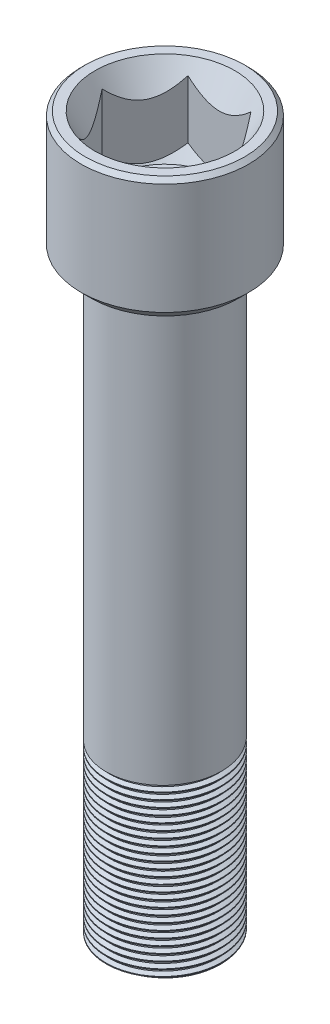
SolidWorks part; units mm, degrees
ref_plane "Front Plane" through (0, 0, 0) normal (0, 0, 1) x (1, 0, 0)
ref_plane "Top Plane" through (0, 0, 0) normal (0, 1, 0) x (1, 0, 0)
ref_plane "Right Plane" through (0, 0, 0) normal (1, 0, 0) x (0, 0, -1)
sketch "Sketch1" plane through (0, 0, 0) normal (0, 1, 0) x (1, 0, 0)
  circle A0 centre (0, 0) radius 4
  dimension "D1" = 8
extrude "Boss-Extrude1" add sketch "Sketch1" against normal blind 12
sketch "Sketch2" plane through (0, -12, 0) normal (0, -1, 0) x (1, 0, 0)
  circle A0 centre (0, 0) radius 2.75
  dimension "D1" = 5.5
extrude "Boss-Extrude2" add sketch "Sketch2" along normal blind 30
sketch "Sketch3" plane through (0, 0, 0) normal (0, 1, 0) x (1, 0, 0)
  line L1 (4.5, 0) -> (2.25, 3.8971)
  line L2 (2.25, 3.8971) -> (-2.25, 3.8971)
  line L3 (-2.25, 3.8971) -> (-4.5, 0)
  line L4 (-4.5, 0) -> (-2.25, -3.8971)
  line L5 (-2.25, -3.8971) -> (2.25, -3.8971)
  line L6 (2.25, -3.8971) -> (4.5, 0)
  circle A0 centre (0, 0) radius 3.8971 construction
  dimension "D1" = 4.5
extrude "Cut-Extrude1" cut sketch "Sketch3" against normal blind 6
chamfer "Chamfer2" distance 0.5 angle 45 1 edges at (0, -12, 4)
thread "Thread2" pitch 0.3175 method cut profile "Thread Profile6" start angle 0, offset 0, length 0, pitch 0.3175, diameter 5.5
ref_plane "Plane7" through (2.75, -42, 0) normal (0, 0, 1) x (1, 0, 0)
sketch "Thread Profile6" plane through (2.75, -42, 0) normal (0, 0, 1) x (1, 0, 0)
  line L0 (0, 0) -> (0, 0.3175) construction
  line L11 (0, 0) -> (0, 0.2778)
  line L12 (0, 0.2778) -> (-0.1719, 0.1786)
  line L13 (-0.1719, 0.1786) -> (-0.1719, 0.0992)
  line L15 (-0.1719, 0.0992) -> (0, 0)
  line L17 (-0.1719, 0.1389) -> (0, 0.1389) construction
  point P2 (0, 0)
  dimension "Pitch" = 0.3175
  dimension "Profile_Angle" = 60
  dimension "Profile_Land" = 0.0794
  dimension "Profile_Height" = 0.1719
sketch "Sketch59" plane through (0, -42, 0) normal (0, -1, 0) x (1, 0, 0)
  circle A0 centre (0, 0) radius 7.5
  dimension "D1" = 15
extrude "Cut-Extrude2" cut sketch "Sketch59" against normal blind 2
sketch "Sketch60" plane through (0, 0, 0) normal (0, 1, 0) x (1, 0, 0)
  circle A0 centre (0, 0) radius 7.5
  dimension "D1" = 15
extrude "Cut-Extrude3" cut sketch "Sketch60" against normal blind 3
sketch "Sketch61" plane through (0, -6, 0) normal (0, 1, 0) x (1, 0, 0)
  circle A0 centre (0, 0) radius 4.8158
extrude "Cut-Extrude4" cut sketch "Sketch61" along normal blind 10
sketch "Sketch62" plane through (0, -6, 0) normal (0, 1, 0) x (1, 0, 0)
  line L1 (3, 0) -> (1.5, 2.5981)
  line L2 (1.5, 2.5981) -> (-1.5, 2.5981)
  line L3 (-1.5, 2.5981) -> (-3, 0)
  line L4 (-3, 0) -> (-1.5, -2.5981)
  line L5 (-1.5, -2.5981) -> (1.5, -2.5981)
  line L6 (1.5, -2.5981) -> (3, 0)
  circle A0 centre (0, 0) radius 2.5981 construction
  dimension "D1" = 3
extrude "Cut-Extrude5" cut sketch "Sketch62" against normal blind 4
sketch "Sketch64" plane through (0, 0, 0) normal (0, 0, 1) x (1, 0, 0)
  line L0 (-2.4061, -6) -> (-3, -6.9824)
  line L1 (4, -6) -> (-4, -6) construction
  line L2 (-3, -10) -> (-3, -6) construction
  line L3 (-3, -6.9824) -> (-3, -6)
  line L4 (-3, -6) -> (-2.4061, -6)
sketch "Sketch65" plane through (0, 0, 0) normal (0, 0, 1) x (1, 0, 0)
  line L0 (-3, -6) -> (-2.1943, -6)
  line L1 (4, -6) -> (-4, -6) construction
  line L2 (-2.1943, -6) -> (-3, -7.3047)
  line L3 (-3, -10) -> (-3, -6) construction
  line L4 (-3, -7.3047) -> (-3, -6)
chamfer "Chamfer4" distance 0.2 1 edges at (-2.25, -6, -1.299)
chamfer "Chamfer5" distance 0.2 angle 45 1 edges at (-2.3077, -6, 1.199)
chamfer "Chamfer6" distance 0.2 angle 45 1 edges at (-0.1155, -6, -2.5981)
chamfer "Chamfer7" distance 0.2 angle 45 1 edges at (2.1923, -6, -1.399)
chamfer "Chamfer8" distance 0.2 angle 45 2 edges at (-0.1155, -6, 2.5981) (2.3077, -6, 1.199)
chamfer "Chamfer9" distance 0.2 angle 45 1 edges at (0, -6, 4)
sketch "Sketch69" plane through (0, 0, 0) normal (0, 0, 1) x (1, 0, 0)
  line L0 (0, 0) -> (0, -50000) construction
  line L1 (-3, -9.3662) -> (-2.5455, -10)
  line L2 (-3, -10) -> (-3, -6.2) construction
  line L3 (-3, -10) -> (-1.5, -10) construction
  line L4 (-2.5455, -10) -> (-3, -10)
  line L5 (-3, -10) -> (-3, -9.3662)
revolve "Revolve1" add sketch "Sketch69" angle 360 about L0
sketch "Sketch70" plane through (0, 0, 0) normal (0, 0, 1) x (1, 0, 0)
  line L6 (0, 0) -> (0, -50000) construction
  line L8 (-3.5176, -5.7194) -> (-1.0203, -8.057)
  line L9 (-1.0203, -8.057) -> (-1.0203, -5.7194)
  line L10 (-1.0203, -5.7194) -> (-3.5176, -5.7194)
sketch "Sketch71" plane through (0, 0, 0) normal (0, 0, 1) x (1, 0, 0)
  line L0 (0, 0) -> (0, -50000) construction
  line L1 (-3.5281, -5.6564) -> (-1.9269, -8.4971)
  line L2 (-1.9269, -8.4971) -> (-1.9269, -5.6564)
  line L3 (-1.9269, -5.6564) -> (-3.5281, -5.6564)
revolve "Cut-Revolve17" cut sketch "Sketch71" angle 360 about L0
